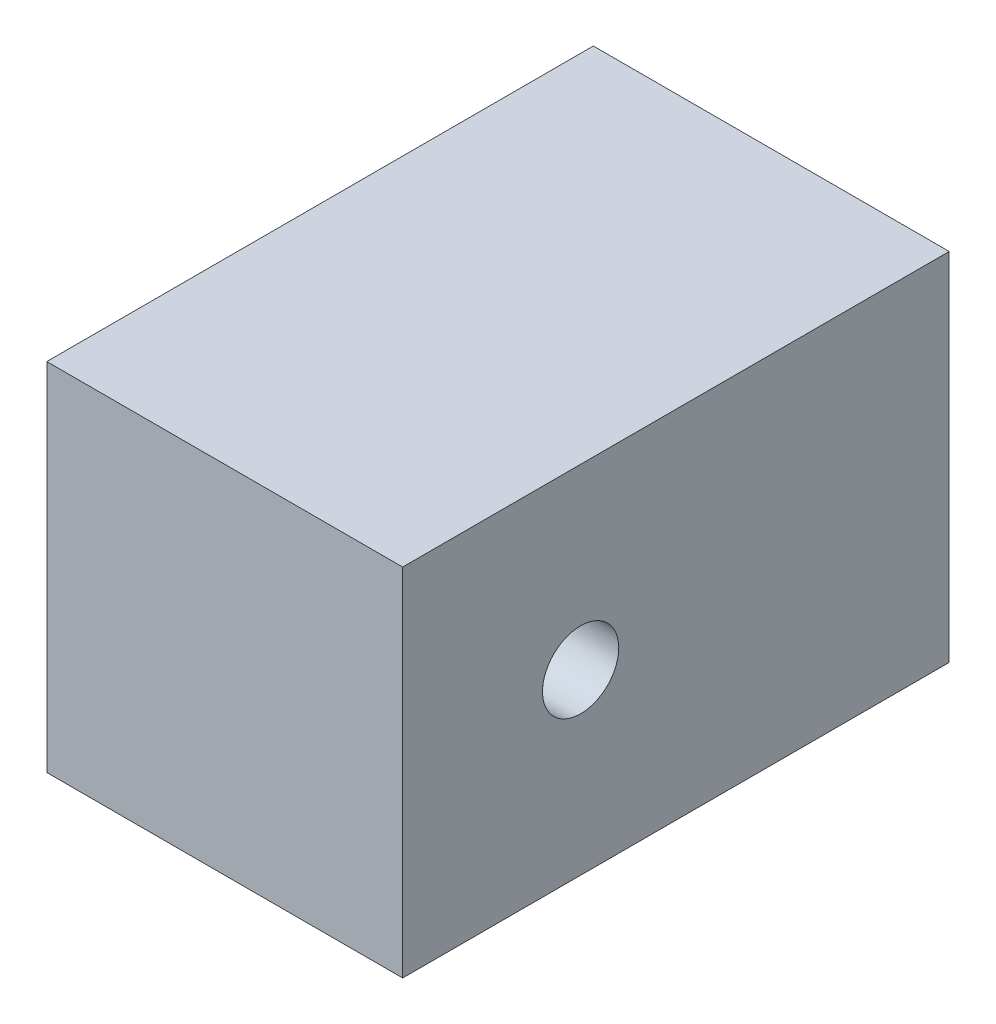
SolidWorks part; units mm, degrees
ref_plane "Alzado" through (0, 0, 0) normal (0, 0, 1) x (1, 0, 0)
ref_plane "Planta" through (0, 0, 0) normal (0, 1, 0) x (1, 0, 0)
ref_plane "Vista lateral" through (0, 0, 0) normal (1, 0, 0) x (0, 0, -1)
sketch "Croquis1" plane through (0, 0, 0) normal (0, 0, 1) x (1, 0, 0)
  line L1 (0, 0) -> (28, 0)
  line L2 (0, 0) -> (0, 28)
  line L3 (0, 28) -> (28, 28)
  line L4 (28, 0) -> (28, 28)
  dimension "D1" = 28
  dimension "D2" = 28
extrude "Saliente-Extruir1" add sketch "Croquis1" along normal blind 28
sketch "Croquis4" plane through (0, 0, 0) normal (-1, 0, 0) x (0, 0, 1)
  line L0 (14, 28) -> (14, 0) construction
  line L1 (28, 28) -> (0, 28) construction
  line L2 (28, 0) -> (0, 0) construction
  line L3 (0, 14) -> (28, 14) construction
  line L4 (0, 28) -> (0, 0) construction
  line L5 (28, 28) -> (28, 0) construction
  circle A0 centre (14, 14) radius 3.175
extrude "Cortar-Extruir3" cut sketch "Croquis4" against normal blind 10
sketch "Croquis6" plane through (28, 0, 0) normal (1, 0, 0) x (0, 0, -1)
  line L0 (-14, 28) -> (-14, 0) construction
  line L1 (-28, 28) -> (0, 28) construction
  line L2 (-28, 0) -> (0, 0) construction
  line L3 (-28, 14) -> (0, 14) construction
  line L4 (-28, 0) -> (-28, 28) construction
  line L5 (0, 0) -> (0, 28) construction
  circle A0 centre (-14, 14) radius 3
extrude "Cortar-Extruir4" cut sketch "Croquis6" against normal blind 10
sketch "Croquis7" plane through (0, 0, 0) normal (0, 0, -1) x (-1, 0, 0)
  line L1 (-28, 0) -> (0, 0)
  line L2 (-28, 0) -> (-28, 28)
  line L3 (-28, 28) -> (0, 28)
  line L4 (0, 0) -> (0, 28)
extrude "Saliente-Extruir2" add sketch "Croquis7" along normal blind 15
